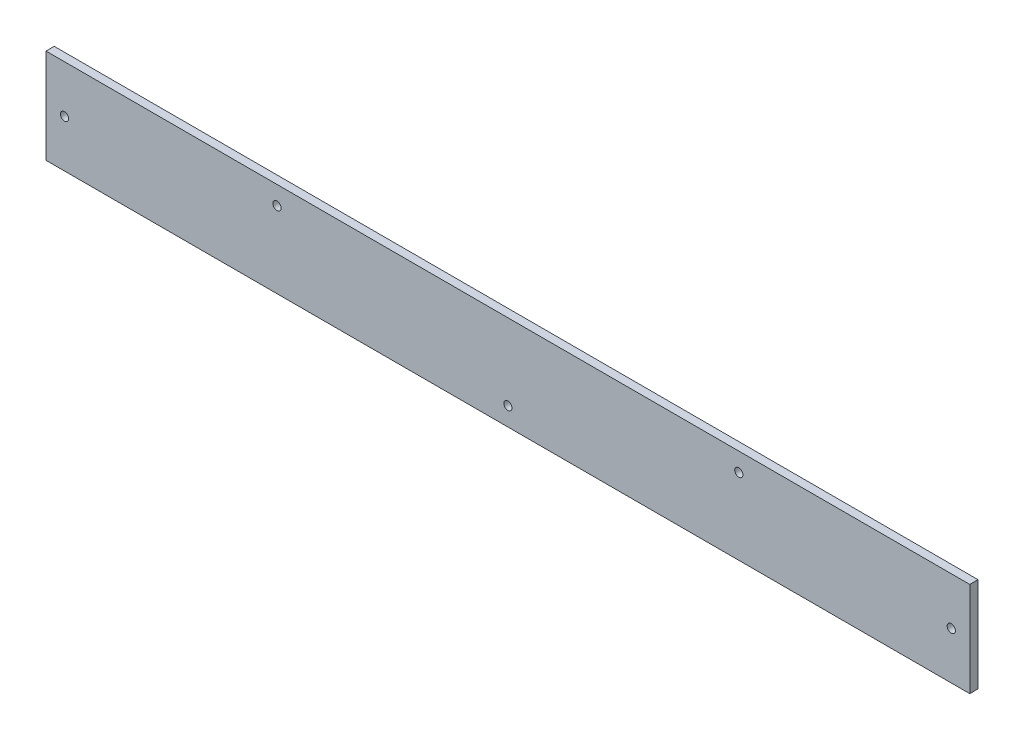
SolidWorks part; units mm, degrees
ref_plane "Piano frontale" through (0, 0, 0) normal (0, 0, 1) x (1, 0, 0)
ref_plane "Piano superiore" through (0, 0, 0) normal (0, 1, 0) x (1, 0, 0)
ref_plane "Piano destro" through (0, 0, 0) normal (1, 0, 0) x (0, 0, -1)
sketch "Schizzo1" plane through (0, 0, 0) normal (0, 0, 1) x (1, 0, 0)
  line L0 (0, 0) -> (0, 46)
  line L1 (0, 46) -> (449, 46)
  line L2 (449, 46) -> (449, 0)
  line L3 (449, 0) -> (0, 0)
  line L4 (0, 23) -> (449, 23) construction
  line L5 (224.5, 42) -> (224.5, 123.488) construction
  line L6 (0, 0) -> (224.5, 46) construction
  line L7 (112.25, 23) -> (112.25, 46) construction
  circle A0 centre (9, 23) radius 2
  circle A1 centre (112.25, 37) radius 2
  circle A2 centre (224.5, 9) radius 2
  circle A3 centre (440, 23) radius 2
  circle A4 centre (336.75, 37) radius 2
  dimension "D3" = 9
  dimension "D4" = 9
  dimension "D6" = 4
  dimension "D5" = 4
  dimension "D8" = 4
  dimension "D9" = 4
  dimension "D1" = 46
  dimension "D2" = 449
  dimension "D7" = 9
  dimension "D10" = 9
extrude "Estrusione-Estrusione1" add sketch "Schizzo1" along normal blind 4
